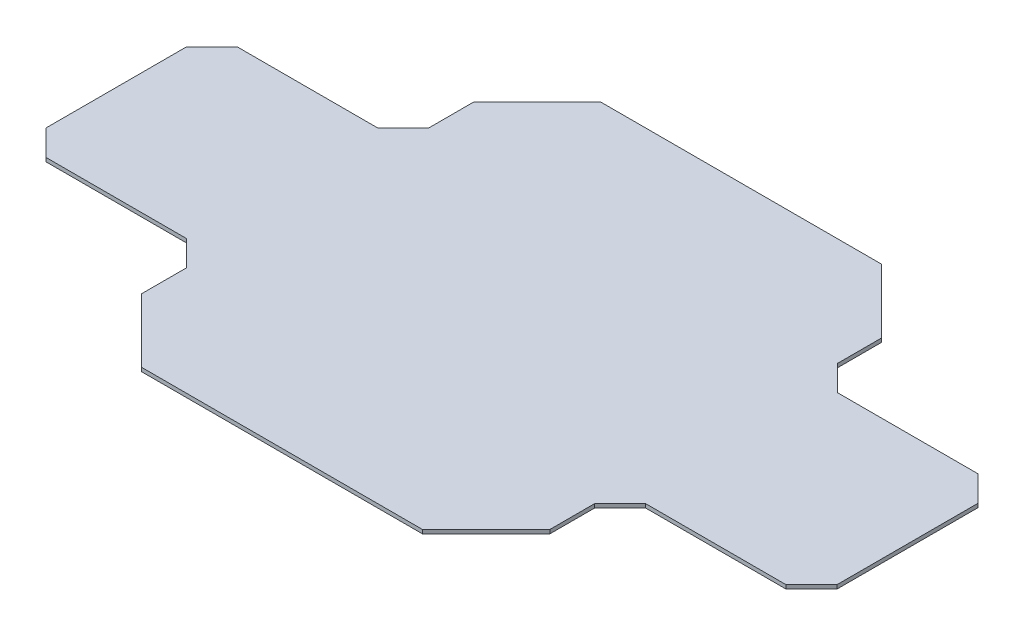
SolidWorks part; units mm, degrees
ref_plane "前视基准面" through (0, 0, 0) normal (0, 0, 1) x (1, 0, 0)
ref_plane "上视基准面" through (0, 0, 0) normal (0, 1, 0) x (1, 0, 0)
ref_plane "右视基准面" through (0, 0, 0) normal (1, 0, 0) x (0, 0, -1)
sketch "草图1" plane through (0, 0, 0) normal (0, 1, 0) x (1, 0, 0)
  line L0 (-310, 75) -> (310, -75) construction
  line L1 (-260, 200) -> (260, 200) construction
  line L2 (-260, 200) -> (-260, -200) construction
  line L3 (-260, -200) -> (260, -200) construction
  line L4 (260, 200) -> (260, -200) construction
  line L5 (310, 75.5001) -> (-310, -75) construction
  line L6 (-160, 200) -> (160, -200) construction
  line L7 (-310, -75) -> (-160, -75)
  line L8 (-310, -75) -> (-310, 75)
  line L9 (-310, 75) -> (-160, 75)
  line L10 (310, -75) -> (310, 75.5001)
  line L11 (160, 200) -> (-160, -200) construction
  line L13 (-160, -200) -> (160, -200)
  line L14 (-160, -200) -> (-160, -75)
  line L15 (-160, 200) -> (160, 200)
  line L16 (160, -200) -> (160, -75)
  line L19 (-160, 75) -> (-160, 200)
  line L22 (160, 75.5001) -> (310, 75.5001)
  line L25 (160, 75.5001) -> (160, 200)
  line L28 (160, -75) -> (310, -75)
  point P0 (0, 0)
  point P6 (-0.5159, 0.1248)
  point P11 (0, 0)
  dimension "D1" = 520
  dimension "D2" = 400
  dimension "D3" = 50
  dimension "D4" = 125
  dimension "D5" = 100
extrude "凸台-拉伸1" add sketch "草图1" along normal blind 3
chamfer "倒角1" distance 20 angle 45 8 edges at (-160, 1.5, -75) (-310, 1.5, -75) (-310, 1.5, 75) (-160, 1.5, 75) (160, 1.5, 75) (160, 1.5, -75.5001) (310, 1.5, 75) (310, 1.5, -75.5001)
sketch "草图2" plane through (0, 3, 0) normal (0, 1, 0) x (1, 0, 0)
  line L0 (-160, 200) -> (-160, 95) construction
  line L1 (-160, 180) -> (160, 180)
  line L2 (-160, 180) -> (-160, 200)
  line L3 (-160, 200) -> (160, 200)
  line L4 (160, 180) -> (160, 200)
  line L6 (160, -200) -> (-160, -200)
  line L7 (160, -200) -> (160, -180)
  line L8 (160, -180) -> (-160, -180)
  line L9 (-160, -200) -> (-160, -180)
  dimension "D1" = 20
  dimension "D2" = 20
extrude "切除-拉伸1" cut sketch "草图2" against normal blind 5
chamfer "倒角2" distance 50 angle 45 4 edges at (-160, 1.5, -180) (-160, 1.5, 180) (160, 1.5, -180) (160, 1.5, 180)
